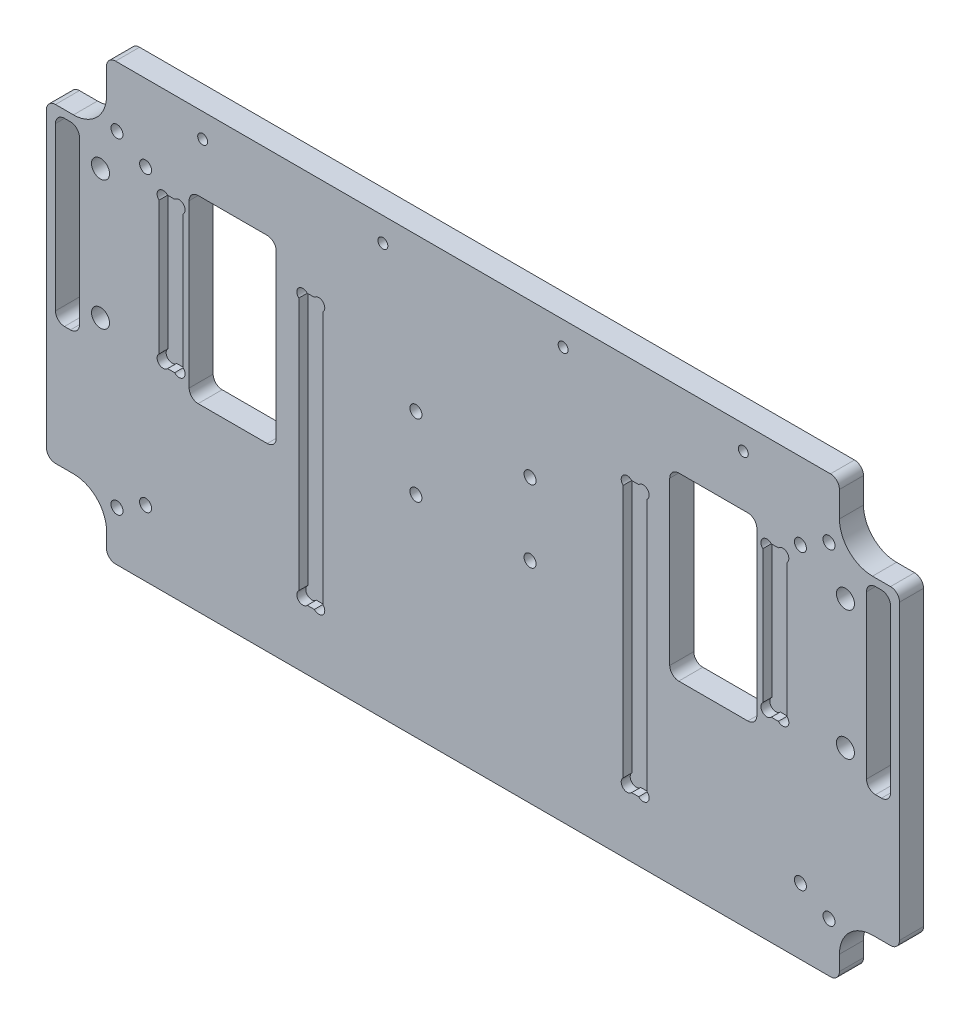
SolidWorks part; units mm, degrees
ref_plane "Front" through (0, 0, 0) normal (0, 0, 1) x (1, 0, 0)
ref_plane "Top" through (0, 0, 0) normal (0, 1, 0) x (1, 0, 0)
ref_plane "Right" through (0, 0, 0) normal (1, 0, 0) x (0, 0, -1)
sketch "Esquisse1" plane through (0, 0, 0) normal (0, 0, 1) x (1, 0, 0)
  line L1 (0, 0) -> (284, 0)
  line L2 (0, 0) -> (0, 145)
  line L3 (0, 145) -> (284, 145)
  line L4 (284, 0) -> (284, 145)
  dimension "D1" = 284
  dimension "D2" = 145
extrude "Boss.-Extru.1" add sketch "Esquisse1" along normal blind 8
sketch "Esquisse2" plane through (0, 0, 8) normal (0, 0, 1) x (1, 0, 0)
  line L0 (142, 145) -> (142, 0) construction
  line L1 (47.5, 60) -> (76.5, 60)
  line L2 (47.5, 60) -> (47.5, 120)
  line L3 (47.5, 120) -> (76.5, 120)
  line L4 (76.5, 60) -> (76.5, 120)
  line L5 (284, 145) -> (0, 145) construction
  line L6 (0, 0) -> (284, 0) construction
  line L7 (76.5, 90) -> (142, 90) construction
  line L8 (62, 60) -> (62, 120) construction
  line L9 (47.5, 90) -> (11, 90) construction
  line L10 (7, 60) -> (7, 120) construction
  line L11 (3, 60) -> (11, 60)
  line L12 (3, 60) -> (3, 120)
  line L13 (3, 120) -> (11, 120)
  line L14 (11, 60) -> (11, 120)
  line L15 (277, 60) -> (277, 120) construction
  line L16 (236.5, 90) -> (273, 90) construction
  line L17 (222, 60) -> (222, 120) construction
  line L18 (273, 60) -> (273, 120)
  line L19 (281, 120) -> (273, 120)
  line L20 (281, 60) -> (281, 120)
  line L21 (281, 60) -> (273, 60)
  line L22 (207.5, 60) -> (207.5, 120)
  line L23 (236.5, 120) -> (207.5, 120)
  line L24 (236.5, 60) -> (236.5, 120)
  line L25 (236.5, 60) -> (207.5, 60)
  dimension "D1" = 55
  dimension "D2" = 60
  dimension "D3" = 29
  dimension "D4" = 160
  dimension "D5" = 8
  dimension "D6" = 60
  dimension "D7" = 270
extrude "Enlèv. mat.-Extru.1" cut sketch "Esquisse2" against normal through all
sketch "Esquisse3" plane through (0, 0, 8) normal (0, 0, 1) x (1, 0, 0)
  line L0 (0, 137) -> (284, 137) construction
  line L1 (0, 145) -> (0, 0) construction
  line L2 (284, 0) -> (284, 145) construction
  line L3 (112, 137) -> (112, 180.3897) construction
  line L5 (172, 137) -> (172, 180.3897) construction
  line L6 (172, 180.3897) -> (112, 180.3897) construction
  line L7 (142, 180.3897) -> (142, 145) construction
  line L8 (284, 145) -> (0, 145) construction
  circle A0 centre (112, 137) radius 1.65
  circle A1 centre (172, 137) radius 1.65
  circle A2 centre (232, 137) radius 1.65
  circle A4 centre (52, 137) radius 1.65
  dimension "D1" = 3.3
  dimension "D2" = 4
  dimension "D3" = 8
  dimension "D4" = 60
extrude "Enlèv. mat.-Extru.2" cut sketch "Esquisse3" against normal up to vertex (8 mm away) up to point (284, 145, 0)
sketch "Esquisse4" plane through (0, 0, 8) normal (0, 0, 1) x (1, 0, 0)
  line L0 (142, 0) -> (142, 145) construction
  line L1 (84, 110) -> (92, 110)
  line L2 (84, 110) -> (84, 20)
  line L3 (84, 20) -> (92, 20)
  line L4 (92, 110) -> (92, 20)
  line L5 (0, 0) -> (284, 0) construction
  line L6 (284, 145) -> (0, 145) construction
  line L8 (76.5, 60) -> (76.5, 120) construction
  line L9 (192, 110) -> (192, 20)
  line L10 (200, 20) -> (192, 20)
  line L11 (200, 110) -> (200, 20)
  line L12 (200, 110) -> (192, 110)
  line L13 (47.5, 120) -> (47.5, 60) construction
  line L14 (37.5, 115) -> (45.5, 115)
  line L15 (37.5, 115) -> (37.5, 65)
  line L16 (37.5, 65) -> (45.5, 65)
  line L17 (45.5, 115) -> (45.5, 65)
  line L18 (45.5, 90) -> (47.5, 90) construction
  line L19 (238.5, 90) -> (236.5, 90) construction
  line L20 (238.5, 115) -> (238.5, 65)
  line L21 (246.5, 65) -> (238.5, 65)
  line L22 (246.5, 115) -> (246.5, 65)
  line L23 (246.5, 115) -> (238.5, 115)
  line L24 (47.5, 60) -> (76.5, 60) construction
  dimension "D1" = 40
  dimension "D2" = 90
  dimension "D3" = 8
  dimension "D4" = 7.5
  dimension "D5" = 8
  dimension "D6" = 2
  dimension "D7" = 50
extrude "Enlèv. mat.-Extru.3" cut sketch "Esquisse4" against normal blind 3
sketch "Esquisse5" plane through (0, 0, 8) normal (0, 0, 1) x (1, 0, 0)
  line L0 (142, 0) -> (142, 124.0722) construction
  line L2 (142, 82) -> (121.1311, 82) construction
  line L3 (0, 145) -> (0, 0) construction
  circle A0 centre (123, 94) radius 2
  circle A1 centre (123, 70) radius 2
  circle A2 centre (161, 70) radius 2
  circle A3 centre (161, 94) radius 2
  circle A5 centre (112, 137) radius 1.65 construction
  dimension "D1" = 38
  dimension "D2" = 4
  dimension "D3" = 24
  dimension "D4" = 55
  dimension "D5" = 142
extrude "Enlèv. mat.-Extru.4" cut sketch "Esquisse5" against normal through all
sketch "Esquisse6" plane through (0, 0, 8) normal (0, 0, 1) x (1, 0, 0)
  line L0 (142, 0) -> (142, 119.0936) construction
  line L1 (0, 0) -> (284, 0) construction
  line L2 (11, 90) -> (29.8915, 90) construction
  line L4 (11, 60) -> (11, 120) construction
  line L5 (273, 90) -> (254.1085, 90) construction
  circle A0 centre (18, 111.5) radius 3
  circle A1 centre (18, 68.5) radius 3
  circle A2 centre (266, 68.5) radius 3
  circle A3 centre (266, 111.5) radius 3
  dimension "D3" = 6
  dimension "D1" = 21.5
  dimension "D2" = 7
extrude "Enlèv. mat.-Extru.5" cut sketch "Esquisse6" against normal through all
sketch "Esquisse8" plane through (0, 0, 8) normal (0, 0, 1) x (1, 0, 0)
  line L0 (142, 145) -> (142, 109.7669) construction
  line L1 (0, 145) -> (20, 145)
  line L2 (0, 145) -> (0, 122.5)
  line L3 (0, 122.5) -> (20, 122.5)
  line L4 (20, 145) -> (20, 122.5)
  line L5 (284, 145) -> (0, 145) construction
  line L6 (264, 145) -> (264, 122.5)
  line L7 (284, 122.5) -> (264, 122.5)
  line L8 (284, 145) -> (284, 122.5)
  line L9 (284, 145) -> (264, 145)
  line L10 (264, 0) -> (264, 19)
  line L11 (0, 0) -> (20, 0)
  line L12 (0, 0) -> (0, 19)
  line L13 (0, 19) -> (20, 19)
  line L14 (20, 0) -> (20, 19)
  line L15 (284, 19) -> (264, 19)
  line L16 (284, 0) -> (284, 19)
  line L17 (284, 0) -> (264, 0)
  dimension "D1" = 22.5
  dimension "D2" = 20
  dimension "D3" = 19
extrude "Enlèv. mat.-Extru.7" cut sketch "Esquisse8" against normal through all
fillet "Congé1" radius 11 4 edges at (20, 122.5, 4) (264, 122.5, 4) (264, 19, 4) (20, 19, 4)
sketch "Esquisse7" plane through (0, 0, 8) normal (0, 0, 1) x (1, 0, 0)
  line L0 (142, 145) -> (142, 7.3256) construction
  line L1 (264, 145) -> (20, 145) construction
  line L2 (23.4737, 125) -> (33, 119.5) construction
  line L4 (260.5263, 125) -> (251, 119.5) construction
  line L5 (33, 119.5) -> (33, 22) construction
  line L6 (33, 70.75) -> (100.6533, 70.75) construction
  line L7 (23.4737, 16.5) -> (33, 22) construction
  line L8 (20, 0) -> (264, 0) construction
  line L9 (260.5263, 16.5) -> (251, 22) construction
  circle A0 centre (33, 119.5) radius 2
  circle A1 centre (23.4737, 125) radius 2
  circle A2 centre (260.5263, 125) radius 2
  circle A3 centre (251, 119.5) radius 2
  circle A4 centre (18, 111.5) radius 3 construction
  circle A5 centre (23.4737, 16.5) radius 2
  circle A6 centre (33, 22) radius 2
  circle A7 centre (251, 22) radius 2
  circle A8 centre (260.5263, 16.5) radius 2
  dimension "D1" = 4
  dimension "D2" = 11
  dimension "D3" = 109
  dimension "D4" = 30
  dimension "D5" = 8
  dimension "D6" = 22
extrude "Enlèv. mat.-Extru.6" cut sketch "Esquisse7" against normal through all
fillet "Congé2" radius 3 16 edges at (281, 60, 4) (273, 60, 4) (281, 120, 4) (273, 120, 4) (236.5, 120, 4) (207.5, 120, 4) (236.5, 60, 4) (207.5, 60, 4) (76.5, 60, 4) (47.5, 60, 4) (76.5, 120, 4) (47.5, 120, 4) (11, 120, 4) (3, 120, 4) (3, 60, 4) (11, 60, 4)
sketch "Esquisse9" plane through (0, 0, 8) normal (0, 0, 1) x (1, 0, 0)
  line L0 (37.5, 115) -> (38.8435, 113.6565) construction
  line L1 (45.5, 115) -> (37.5, 115) construction
  line L2 (41.5, 115) -> (41.5, 118.2808) construction
  line L3 (45.5, 115) -> (37.5, 115) construction
  line L4 (45.5, 115) -> (44.1565, 113.6565) construction
  line L5 (45.5, 90) -> (42.8729, 90) construction
  line L6 (45.5, 65) -> (45.5, 115) construction
  line L7 (45.5, 65) -> (44.1565, 66.3435) construction
  line L8 (37.5, 65) -> (38.8435, 66.3435) construction
  line L9 (45.5, 90) -> (238.5, 90) construction
  line L10 (238.5, 115) -> (238.5, 65) construction
  line L11 (142, 90) -> (142, 121.5895) construction
  line L12 (246.5, 65) -> (245.1565, 66.3435) construction
  line L13 (238.5, 65) -> (239.8435, 66.3435) construction
  line L14 (238.5, 90) -> (241.1271, 90) construction
  line L15 (238.5, 115) -> (239.8435, 113.6565) construction
  line L16 (242.5, 115) -> (242.5, 118.2808) construction
  line L17 (246.5, 115) -> (245.1565, 113.6565) construction
  line L18 (84, 110) -> (85.3435, 108.6565) construction
  line L19 (92, 110) -> (84, 110) construction
  line L20 (88, 110) -> (88, 112.2434) construction
  line L21 (92, 110) -> (84, 110) construction
  line L22 (92, 110) -> (90.6565, 108.6565) construction
  line L23 (84, 65) -> (89.3356, 65) construction
  line L24 (84, 110) -> (84, 20) construction
  line L25 (92, 20) -> (90.6565, 21.3435) construction
  line L26 (88, 20) -> (88, 17.7566) construction
  line L27 (84, 20) -> (85.3435, 21.3435) construction
  line L28 (200, 20) -> (198.6565, 21.3435) construction
  line L29 (196, 20) -> (196, 17.7566) construction
  line L30 (192, 20) -> (193.3435, 21.3435) construction
  line L31 (200, 65) -> (194.6644, 65) construction
  line L32 (192, 110) -> (193.3435, 108.6565) construction
  line L33 (196, 110) -> (196, 112.2434) construction
  line L34 (200, 110) -> (198.6565, 108.6565) construction
  circle A0 centre (38.8435, 113.6565) radius 2
  circle A1 centre (44.1565, 113.6565) radius 2
  circle A2 centre (44.1565, 66.3435) radius 2
  circle A3 centre (38.8435, 66.3435) radius 2
  circle A4 centre (245.1565, 66.3435) radius 2
  circle A5 centre (239.8435, 66.3435) radius 2
  circle A6 centre (239.8435, 113.6565) radius 2
  circle A7 centre (245.1565, 113.6565) radius 2
  circle A8 centre (85.3435, 108.6565) radius 2
  circle A9 centre (90.6565, 108.6565) radius 2
  circle A10 centre (90.6565, 21.3435) radius 2
  circle A11 centre (85.3435, 21.3435) radius 2
  circle A12 centre (198.6565, 21.3435) radius 2
  circle A13 centre (193.3435, 21.3435) radius 2
  circle A14 centre (193.3435, 108.6565) radius 2
  circle A15 centre (198.6565, 108.6565) radius 2
  dimension "D1" = 4
  dimension "D6" = 4
  dimension "D2" = 45
  dimension "D3" = 1.9
  dimension "D4" = 45
  dimension "D5" = 1.9
extrude "Enlèv. mat.-Extru.8" cut sketch "Esquisse9" against normal up to vertex (3 mm away) up to point (37.5, 65, 5)
fillet "Congé3" radius 3 8 edges at (264, 145, 4) (284, 122.5, 4) (284, 19, 4) (264, 0, 4) (20, 0, 4) (0, 19, 4) (0, 122.5, 4) (20, 145, 4)
